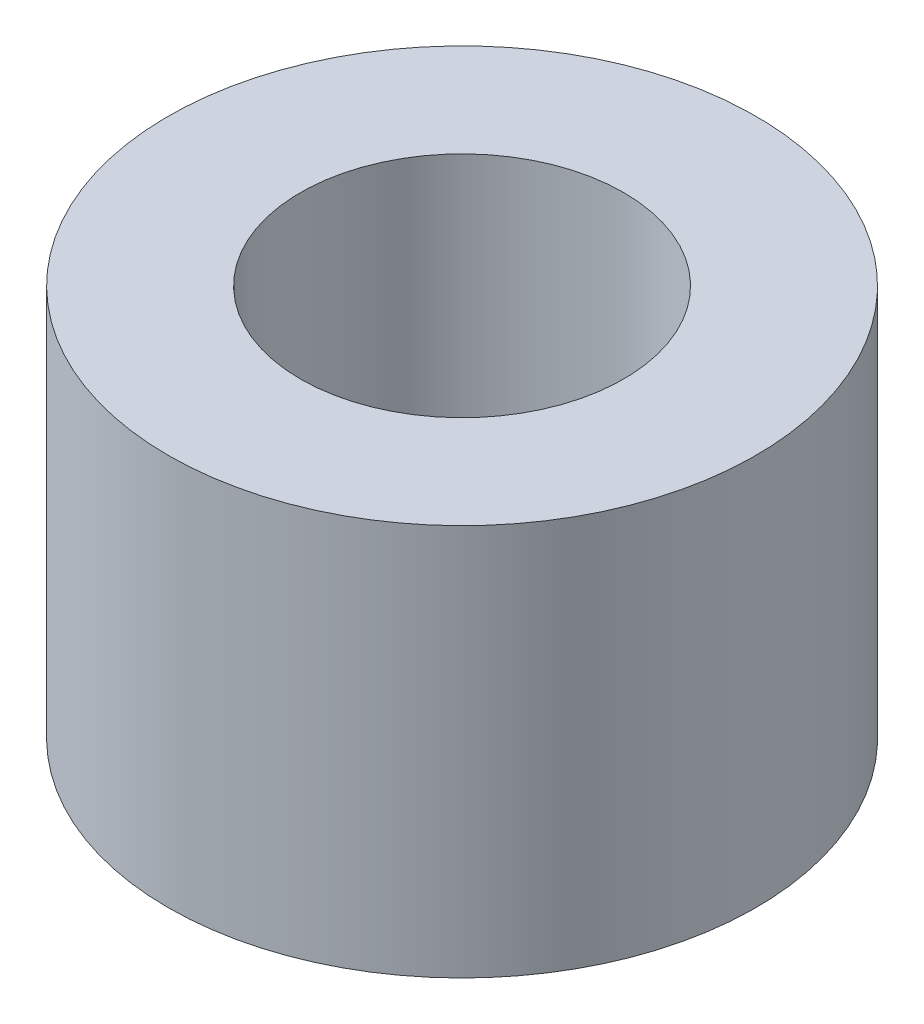
SolidWorks part; units mm, degrees
material "Brass"
ref_plane "Front Plane" through (0, 0, 0) normal (0, 0, 1) x (1, 0, 0)
ref_plane "Top Plane" through (0, 0, 0) normal (0, 1, 0) x (1, 0, 0)
ref_plane "Right Plane" through (0, 0, 0) normal (1, 0, 0) x (0, 0, -1)
sketch "Sketch1" plane through (0, 0, 0) normal (0, 1, 0) x (1, 0, 0)
  circle A0 centre (0, 0) radius 3
  dimension "D1" = 6
extrude "Boss-Extrude1" add sketch "Sketch1" along normal blind 4
hole_wizard "M4x0.7 Tapped Hole1" positions "Sketch2" profile "Sketch3" tap size "M4x0.7" standard "ANSI Metric" end condition through all
sketch "Sketch2" plane through (0, 4, 0) normal (0, 1, 0) x (1, 0, 0)
  point P0 (0, 0)
sketch "Sketch3" plane through (0, 4, 0) normal (1, 0, 0) x (0, 0, 1)
  line L0 (0, 0) -> (0, 4)
  line L1 (0, 4) -> (1.65, 4)
  line L2 (1.65, 4) -> (1.65, 0)
  line L5 (1.65, 0) -> (0, 0)
  line L11 (0, -6.35) -> (0, 107.95) construction
  dimension "Thru Tap Drill Dia." = 3.3
  dimension "Thru Tap Drill Depth" = 4
cosmetic thread "Hole Thread1" parameters "D2"=4
